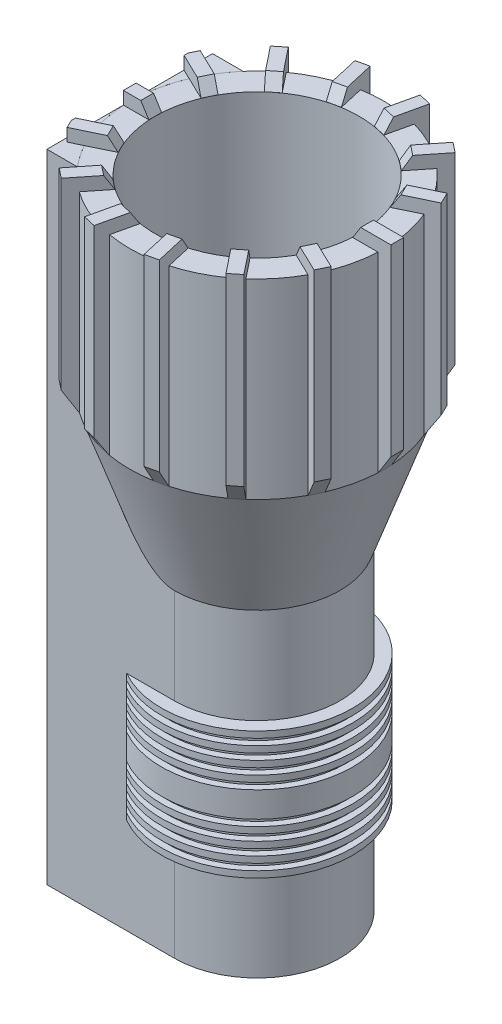
SolidWorks part; units mm, degrees
ref_plane "Front Plane" through (0, 0, 0) normal (0, 0, 1) x (1, 0, 0)
ref_plane "Top Plane" through (0, 0, 0) normal (0, 1, 0) x (1, 0, 0)
ref_plane "Right Plane" through (0, 0, 0) normal (1, 0, 0) x (0, 0, -1)
sketch "Sketch1" plane through (0, 0, 0) normal (0, 1, 0) x (1, 0, 0)
  circle A0 centre (0, 0) radius 6.5
  dimension "D1" = 13
extrude "Boss-Extrude1" add sketch "Sketch1" along normal blind 25
sketch "Sketch2" plane through (0, 0, 0) normal (0, 0, 1) x (1, 0, 0)
  line L0 (0, 0) -> (0, 50) construction
  line L1 (6.5, 25) -> (10, 35)
  line L2 (10, 35) -> (10, 50)
  line L3 (10, 50) -> (0, 50)
  line L4 (0, 50) -> (0, 25)
  line L5 (0, 25) -> (6.5, 25)
  line L6 (6.5, 25) -> (-6.5, 25) construction
  dimension "D1" = 10
  dimension "D2" = 15
revolve "Revolve1" add sketch "Sketch2" angle 360 about L0
shell "Shell1" thickness 2 removed face at (10, 50, 0)
ref_plane "Plane1" through (-10, 0, 0) normal (-1, 0, 0) x (0, 0, 1)
sketch "Sketch3" plane through (-10, 0, 0) normal (-1, 0, 0) x (0, 0, 1)
  line L0 (8, 50) -> (-8, 50) construction
  line L1 (-6.5, 0) -> (6.5, 0)
  line L2 (-6.5, 0) -> (-6.5, 50)
  line L3 (-6.5, 50) -> (6.5, 50)
  line L4 (6.5, 0) -> (6.5, 50)
  line L5 (6.5, 0) -> (6.5, 25) construction
extrude "Boss-Extrude2" add sketch "Sketch3" against normal up to next separate body
sketch "Sketch4" plane through (0, 0, 0) normal (0, -1, 0) x (1, 0, 0)
  circle A0 centre (0, 0) radius 4
  dimension "D1" = 8
extrude "Cut-Extrude1" cut sketch "Sketch4" against normal up to next (2 mm away)
sketch "Sketch5" plane through (0, 0, 0) normal (0, 0, 1) x (1, 0, 0)
  line L0 (6.5, 0) -> (6.5, 25) construction
  line L1 (6.5, 7.5) -> (7.5, 7.5)
  line L2 (6.5, 7.5) -> (6.5, 17.5)
  line L3 (6.5, 17.5) -> (7.5, 17.5)
  line L4 (7.5, 7.5) -> (7.5, 17.5)
  line L5 (0, 0) -> (0, 25) construction
  line L6 (0, 50) -> (0, 0) construction
  line L7 (10, 50) -> (-10, 50) construction
  point P6 (6.5, 12.5)
  point P9 (0, 12.5)
  dimension "D1" = 10
  dimension "D2" = 1
revolve "Revolve2" add sketch "Sketch5" angle 360 about L6
sketch "Sketch6" plane through (0, 0, 0) normal (0, 0, 1) x (1, 0, 0)
  line L0 (7.5, 7.5) -> (7.5, 17.5) construction
  line L1 (7.5, 17) -> (7, 17)
  line L2 (7.5, 17) -> (7.5, 16.5)
  line L3 (7.5, 16.5) -> (7, 16.5)
  line L4 (7, 17) -> (7, 16.5)
  line L5 (-3.7417, 12.5) -> (7.5, 12.5) construction
  line L6 (-3.7417, 7.5) -> (-3.7417, 17.5) construction
  line L7 (7.5, 17.5) -> (-3.7417, 17.5) construction
  line L8 (7.5, 16) -> (7.5, 15.5)
  line L9 (7.5, 16) -> (7, 16)
  line L10 (7, 16) -> (7, 15.5)
  line L11 (7.5, 15.5) -> (7, 15.5)
  line L12 (7.5, 15) -> (7.5, 14.5)
  line L13 (7.5, 15) -> (7, 15)
  line L14 (7, 15) -> (7, 14.5)
  line L15 (7.5, 14.5) -> (7, 14.5)
  line L16 (7.5, 14) -> (7.5, 13.5)
  line L17 (7.5, 14) -> (7, 14)
  line L18 (7, 14) -> (7, 13.5)
  line L19 (7.5, 13.5) -> (7, 13.5)
  line L20 (7.5, 8) -> (7.5, 8.5)
  line L21 (7.5, 8) -> (7, 8)
  line L22 (7, 8) -> (7, 8.5)
  line L23 (7.5, 8.5) -> (7, 8.5)
  line L24 (7.5, 9) -> (7, 9)
  line L25 (7.5, 9) -> (7.5, 9.5)
  line L26 (7.5, 9.5) -> (7, 9.5)
  line L27 (7, 9) -> (7, 9.5)
  line L28 (7.5, 10) -> (7, 10)
  line L29 (7.5, 10) -> (7.5, 10.5)
  line L30 (7, 10) -> (7, 10.5)
  line L31 (7.5, 10.5) -> (7, 10.5)
  line L32 (7.5, 11) -> (7.5, 11.5)
  line L33 (7.5, 11.5) -> (7, 11.5)
  line L34 (7, 11) -> (7, 11.5)
  line L35 (7.5, 11) -> (7, 11)
  line L36 (0, 50) -> (0, 0) construction
  line L37 (10, 50) -> (-10, 50) construction
  dimension "D1" = 0.5
  dimension "D2" = 0.5
  dimension "D3" = 0.5
  dimension "D5" = 0.5
  dimension "D4" = 4
revolve "Cut-Revolve3" cut sketch "Sketch6" angle 360 about L36
sketch "Sketch7" plane through (0, 0, 0) normal (0, 0, 1) x (1, 0, 0)
  line L0 (8, 50) -> (8.6322, 51)
  line L1 (11, 51) -> (11, 36.5819)
  line L2 (11, 36.5819) -> (10, 35)
  line L4 (8, 50) -> (8, 35)
  line L5 (10, 50) -> (-10, 50) construction
  line L6 (10, 35) -> (-10, 35) construction
  line L7 (10, 35) -> (10, 50) construction
  line L8 (8, 35) -> (10, 35)
  line L9 (8.6322, 51) -> (11, 51)
  dimension "D1" = 2
  dimension "D2" = 1.8714
  dimension "D3" = 1
  dimension "D4" = 1
extrude "Boss-Extrude3" add sketch "Sketch7" along normal mid plane 1
pattern_circular "CirPattern2" count 14 over 360 about axis through (0, 0, 0) along (0, -1, 0) of "Boss-Extrude3"
sketch "Sketch8" plane through (0, 50, 0) normal (0, 1, 0) x (1, 0, 0)
  line L0 (-10, 4.5872) -> (-10, 4.2608)
  line L1 (-9.6937, 5.2232) -> (-10.1276, 4.3222) construction
  line L2 (-10, 0) -> (-10, 6.5) construction
  line L3 (-10.1276, 4.3222) -> (-7.9943, 3.2949) construction
  line L4 (-10, 4.2608) -> (-10.1276, 4.3222)
  line L5 (-10.1276, 4.3222) -> (-10, 4.5872)
  line L6 (-10, 0.5) -> (-10, -0.5)
  line L7 (-10, -0.5) -> (-11, -0.5)
  line L8 (-11, -0.5) -> (-11, 0.5)
  line L9 (-11, 0.5) -> (-10, 0.5)
  line L10 (-10, -4.5872) -> (-10, -4.2608)
  line L11 (-10.1276, -4.3222) -> (-9.6937, -5.2232) construction
  line L12 (-10, -6.5) -> (-10, 0) construction
  line L13 (-10.1276, -4.3222) -> (-7.9943, -3.2949) construction
  line L14 (-10, -4.2608) -> (-10.1276, -4.3222)
  line L15 (-10.1276, -4.3222) -> (-10, -4.5872)
extrude "Cut-Extrude2" cut sketch "Sketch8" against normal through all both and the other way through all
